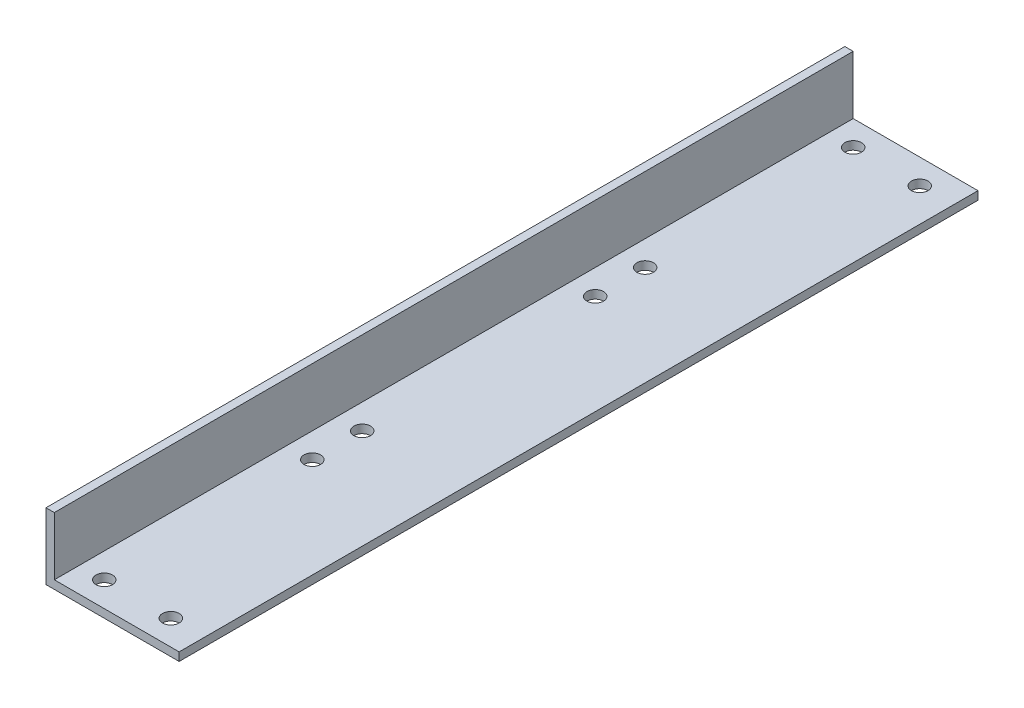
SolidWorks part; units mm, degrees
ref_plane "Front Plane" through (0, 0, 0) normal (0, 0, 1) x (1, 0, 0)
ref_plane "Top Plane" through (0, 0, 0) normal (0, 1, 0) x (1, 0, 0)
ref_plane "Right Plane" through (0, 0, 0) normal (1, 0, 0) x (0, 0, -1)
sketch "Sketch1" plane through (0, 0, 0) normal (0, 0, 1) x (1, 0, 0)
  line L0 (0, 0) -> (50.8, 0)
  line L1 (50.8, 0) -> (50.8, 3.175)
  line L2 (50.8, 3.175) -> (3.175, 3.175)
  line L3 (3.175, 3.175) -> (3.175, 25.4)
  line L4 (3.175, 25.4) -> (0, 25.4)
  line L5 (0, 25.4) -> (0, 0)
  dimension "D1" = 25.4
  dimension "D2" = 50.8
  dimension "D3" = 3.175
  dimension "D4" = 3.175
extrude "Boss-Extrude1" add sketch "Sketch1" along normal blind 304.8
sketch "Sketch2" plane through (0, 0, 0) normal (0, -1, 0) x (1, 0, 0)
  line L0 (0, 0) -> (50.8, 0) construction
  line L1 (0, 304.8) -> (0, 0) construction
  line L2 (0, 152.4) -> (50.8, 152.4)
  line L3 (50.8, 304.8) -> (50.8, 0) construction
  circle A0 centre (38.1, 9.525) radius 3.175
  circle A1 centre (12.7, 9.525) radius 3.175
  circle A4 centre (12.7, 107.95) radius 3.175
  circle A5 centre (12.7, 88.9) radius 3.175
  circle A7 centre (38.1, 295.275) radius 3.175
  circle A8 centre (12.7, 295.275) radius 3.175
  circle A10 centre (12.7, 196.85) radius 3.175
  circle A11 centre (12.7, 215.9) radius 3.175
  point P4 (12.7, 114.3)
  dimension "D1" = 6.35
  dimension "D2" = 88.9
  dimension "D4" = 6.35
  dimension "D9" = 6.35
  dimension "D10" = 6.35
  dimension "D13" = 12.7
  dimension "D5" = 25.4
  dimension "D7" = 9.525
  dimension "D8" = 12.7
  dimension "D11" = 19.05
  dimension "D12" = 63.5
extrude "Cut-Extrude1" cut sketch "Sketch2" against normal through all contours A1 | A0 | A11 | A10 | A4 | A5 | A8 | A7 region at (38.1, 0, 9.525) region at (12.7, 0, 9.525) region at (12.7, 0, 107.95) region at (12.7, 0, 88.9) region at (38.1, 0, 295.275) region at (12.7, 0, 295.275) region at (12.7, 0, 196.85) region at (12.7, 0, 215.9)
